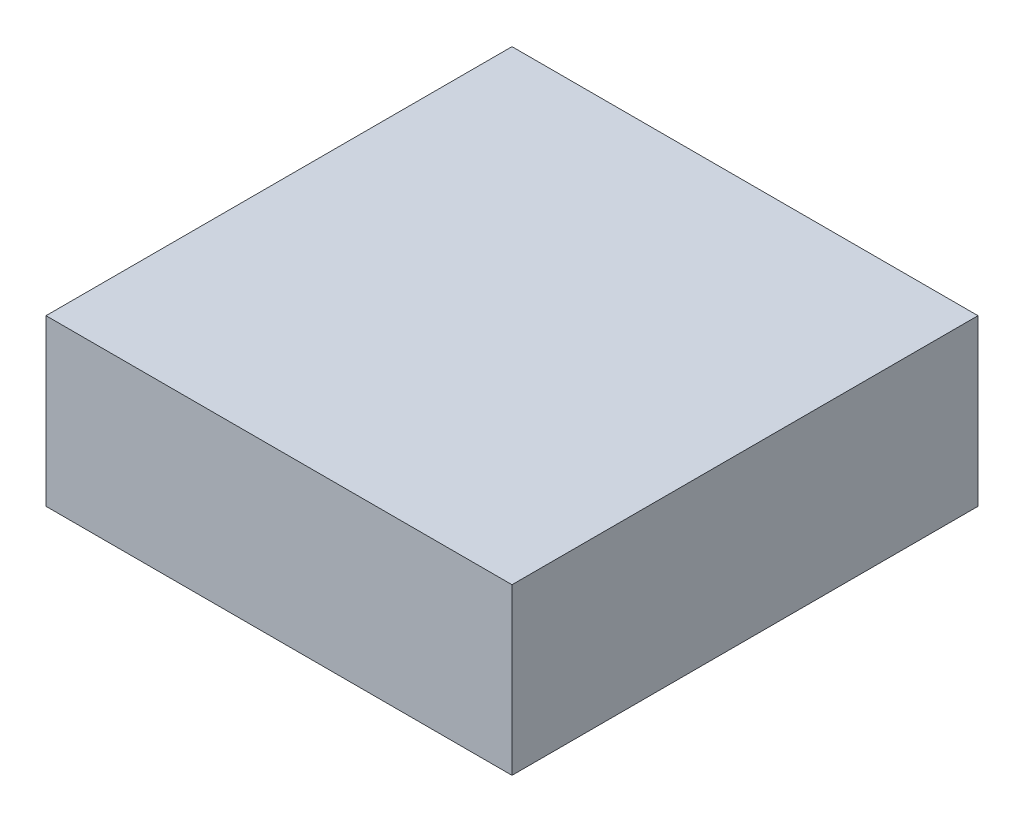
SolidWorks part; units mm, degrees
ref_plane "Front Plane" through (0, 0, 0) normal (0, 0, 1) x (1, 0, 0)
ref_plane "Top Plane" through (0, 0, 0) normal (0, 1, 0) x (1, 0, 0)
ref_plane "Right Plane" through (0, 0, 0) normal (1, 0, 0) x (0, 0, -1)
sketch "Sketch1" plane through (0, 0, 0) normal (0, 1, 0) x (1, 0, 0)
  line L1 (0, 0) -> (127, 0)
  line L2 (0, 0) -> (0, 127)
  line L3 (0, 127) -> (127, 127)
  line L4 (127, 0) -> (127, 127)
  dimension "D1" = 127
  dimension "D2" = 127
extrude "Boss-Extrude1" add sketch "Sketch1" along normal blind 45
